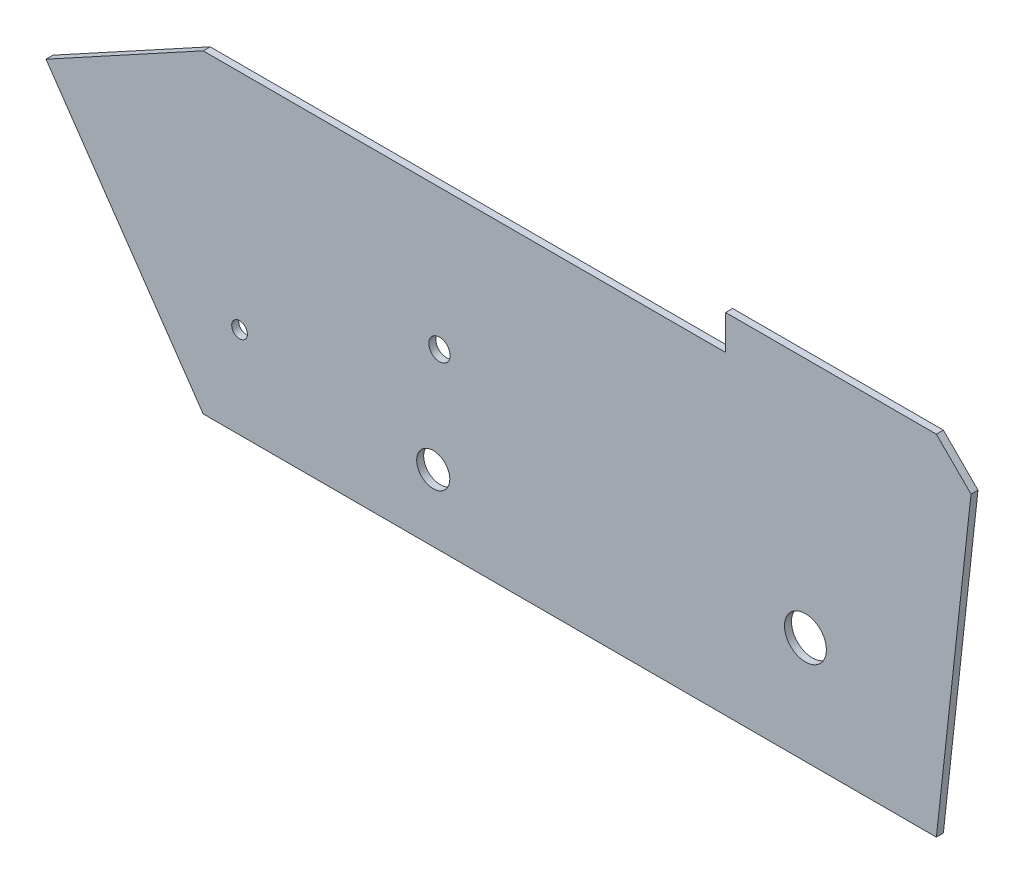
SolidWorks part; units mm, degrees
ref_plane "Front Plane" through (0, 0, 0) normal (0, 0, 1) x (1, 0, 0)
ref_plane "Top Plane" through (0, 0, 0) normal (0, 1, 0) x (1, 0, 0)
ref_plane "Right Plane" through (0, 0, 0) normal (1, 0, 0) x (0, 0, -1)
sketch "Sketch1" plane through (0, 0, 0) normal (0, 0, 1) x (1, 0, 0)
  line L0 (192.0393, 88.9838) -> (201.963, 79.0601)
  line L5 (201.963, 79.0601) -> (192.0393, -11.0162)
  line L6 (192.0393, -11.0162) -> (-18.008, -11.0162)
  line L8 (-18.008, 79.0601) -> (131.6712, 79.0601)
  line L9 (131.6712, 79.0601) -> (131.6712, 88.9838)
  line L10 (131.6712, 88.9838) -> (192.0393, 88.9838)
  line L11 (-18.008, 79.0601) -> (-63.037, 54.4726)
  line L12 (-63.037, 54.4726) -> (-18.008, -11.0162)
extrude "Boss-Extrude1" add sketch "Sketch1" along normal blind 2
sketch "Sketch2" plane through (0, 0, 2) normal (0, 0, 1) x (1, 0, 0)
  circle A0 centre (154.5233, 19.6951) radius 6
  dimension "D1" = 12
extrude "Cut-Extrude1" cut sketch "Sketch2" against normal blind 10
sketch "Sketch3" plane through (0, 0, 2) normal (0, 0, 1) x (1, 0, 0)
  circle A0 centre (49.68, 38.8251) radius 3.05
extrude "Cut-Extrude2" cut sketch "Sketch3" against normal blind 10
sketch "Sketch4" plane through (0, 0, 2) normal (0, 0, 1) x (1, 0, 0)
  circle A0 centre (-7.5862, 15.0785) radius 2.2503
extrude "Cut-Extrude3" cut sketch "Sketch4" against normal blind 10
sketch "Sketch5" plane through (0, 0, 2) normal (0, 0, 1) x (1, 0, 0)
  circle A0 centre (47.9037, 8.1196) radius 4.7404
extrude "Cut-Extrude4" cut sketch "Sketch5" against normal blind 10
